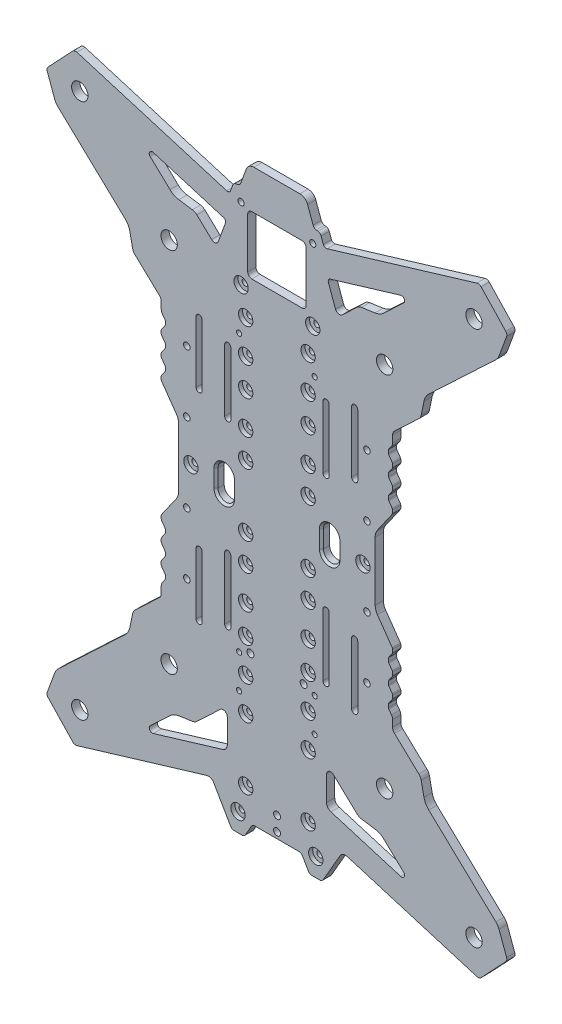
SolidWorks part; units mm, degrees
ref_plane "Front Plane" through (0, 0, 0) normal (0, 0, 1) x (1, 0, 0)
ref_plane "Top Plane" through (0, 0, 0) normal (0, 1, 0) x (1, 0, 0)
ref_plane "Right Plane" through (0, 0, 0) normal (1, 0, 0) x (0, 0, -1)
sketch "Model" plane through (0, 0, 0) normal (0, 0, 1) x (1, 0, 0)
  line L0 (183.8108, 197.417) -> (183.8108, 227.917)
  line L1 (186.8108, 227.917) -> (186.8108, 197.417)
  line L2 (138.8108, 139.917) -> (138.8108, 109.417)
  line L3 (135.8108, 109.417) -> (135.8108, 139.917)
  line L4 (186.8108, 139.917) -> (186.8108, 109.417)
  line L5 (183.8108, 109.417) -> (183.8108, 139.917)
  line L6 (135.8108, 197.417) -> (135.8108, 227.917)
  line L7 (138.8108, 227.917) -> (138.8108, 197.417)
  line L8 (147.0608, 264.0945) -> (147.0608, 288.5945)
  line L9 (173.5608, 262.0945) -> (149.0608, 262.0945)
  line L10 (175.5608, 288.5945) -> (175.5608, 264.0945)
  line L11 (149.0608, 290.5945) -> (173.5608, 290.5945)
  line L12 (133.6884, 72.3677) -> (122.1935, 61.5247)
  line L13 (120.0282, 60.4766) -> (113.4215, 59.5095)
  line L14 (100.8847, 45.7661) -> (134.926, 56.02)
  line L15 (209.2, 59.5095) -> (202.5933, 60.4766)
  line L16 (200.428, 61.5247) -> (188.9331, 72.3677)
  line L17 (185.5608, 58.8925) -> (185.5608, 70.9128)
  line L18 (187.6955, 56.02) -> (221.7368, 45.7661)
  line L19 (223.1987, 48.2935) -> (213.5306, 57.4133)
  line L20 (113.4215, 277.8244) -> (120.0282, 276.8573)
  line L21 (122.1935, 275.8092) -> (129.4288, 268.9842)
  line L22 (135.174, 281.2392) -> (100.8847, 291.5678)
  line L23 (99.4228, 289.0404) -> (109.0909, 279.9206)
  line L24 (261.0344, 314.783) -> (273.0616, 302.0327)
  line L25 (273.4849, 299.9728) -> (269.7846, 289.8648)
  line L26 (268.2674, 287.5628) -> (235.4884, 256.6428)
  line L27 (233.1432, 252.4417) -> (231.7925, 245.9027)
  line L28 (230.6199, 243.8022) -> (218.7522, 232.6075)
  line L29 (217.8108, 230.4252) -> (217.8108, 227.2161)
  line L30 (217.2682, 225.4954) -> (215.9916, 223.6722)
  line L31 (215.8108, 223.0986) -> (215.8108, 221.7292)
  line L32 (215.9916, 221.1557) -> (217.6299, 218.8159)
  line L33 (217.8108, 218.2423) -> (217.8108, 216.8729)
  line L34 (217.6299, 216.2994) -> (215.9916, 213.9596)
  line L35 (215.8108, 213.386) -> (215.8108, 212.0166)
  line L36 (215.9916, 211.4431) -> (217.6299, 209.1033)
  line L37 (217.8108, 208.5298) -> (217.8108, 207.1603)
  line L38 (217.6299, 206.5868) -> (215.9916, 204.247)
  line L39 (215.8108, 203.6735) -> (215.8108, 202.304)
  line L40 (215.9916, 201.7305) -> (217.6299, 199.3907)
  line L41 (217.8108, 198.8172) -> (217.8108, 197.4478)
  line L42 (217.6299, 196.8742) -> (210.3959, 186.5429)
  line L43 (209.3108, 183.1014) -> (209.3108, 154.2325)
  line L44 (210.3959, 150.791) -> (217.6299, 140.4597)
  line L45 (217.8108, 139.8861) -> (217.8108, 138.5167)
  line L46 (217.6299, 137.9432) -> (215.9916, 135.6034)
  line L47 (215.8108, 135.0299) -> (215.8108, 133.6605)
  line L48 (215.9916, 133.0869) -> (217.6299, 130.7471)
  line L49 (217.8108, 130.1736) -> (217.8108, 128.8042)
  line L50 (217.6299, 128.2306) -> (215.9916, 125.8908)
  line L51 (215.8108, 125.3173) -> (215.8108, 123.9479)
  line L52 (215.9916, 123.3743) -> (217.6299, 121.0345)
  line L53 (217.8108, 120.461) -> (217.8108, 119.0916)
  line L54 (217.6299, 118.518) -> (215.9916, 116.1782)
  line L55 (215.8108, 115.6047) -> (215.8108, 114.2353)
  line L56 (215.9916, 113.6617) -> (217.2682, 111.8385)
  line L57 (217.8108, 110.1178) -> (217.8108, 106.9087)
  line L58 (218.7522, 104.7264) -> (230.6199, 93.5317)
  line L59 (231.7925, 91.4312) -> (233.1432, 84.8922)
  line L60 (235.4884, 80.6911) -> (268.2674, 49.7711)
  line L61 (269.7846, 47.4691) -> (273.4849, 37.3611)
  line L62 (273.0616, 35.3012) -> (261.0344, 22.5509)
  line L63 (259.0027, 22.0083) -> (195.64, 41.0944)
  line L64 (192.1766, 39.7219) -> (183.942, 25.4591)
  line L65 (182.2099, 24.4591) -> (178.4116, 24.4591)
  line L66 (176.6796, 25.4591) -> (173.7928, 30.4591)
  line L67 (172.0608, 31.4591) -> (150.5608, 31.4591)
  line L68 (148.8287, 30.4591) -> (145.942, 25.4591)
  line L69 (144.2099, 24.4591) -> (140.4116, 24.4591)
  line L70 (138.6796, 25.4591) -> (130.4449, 39.7219)
  line L71 (126.9816, 41.0944) -> (63.6188, 22.0083)
  line L72 (61.5871, 22.5509) -> (49.5599, 35.3012)
  line L73 (49.1366, 37.3611) -> (52.8369, 47.4691)
  line L74 (54.3542, 49.7711) -> (87.1331, 80.6911)
  line L75 (89.4783, 84.8922) -> (90.8291, 91.4312)
  line L76 (92.0016, 93.5317) -> (103.8693, 104.7264)
  line L77 (104.8108, 106.9087) -> (104.8108, 110.1178)
  line L78 (105.3533, 111.8385) -> (106.6299, 113.6617)
  line L79 (106.8108, 114.2353) -> (106.8108, 115.6047)
  line L80 (106.6299, 116.1782) -> (104.9916, 118.518)
  line L81 (104.8108, 119.0916) -> (104.8108, 120.461)
  line L82 (104.9916, 121.0345) -> (106.6299, 123.3743)
  line L83 (106.6299, 125.8908) -> (104.9916, 128.2306)
  line L84 (104.8108, 128.8042) -> (104.8108, 130.1736)
  line L85 (104.9916, 130.7471) -> (106.6299, 133.0869)
  line L86 (106.8108, 133.6605) -> (106.8108, 135.0299)
  line L87 (106.6299, 135.6034) -> (104.9916, 137.9432)
  line L88 (104.8108, 138.5167) -> (104.8108, 139.8861)
  line L89 (104.9916, 140.4597) -> (112.2257, 150.791)
  line L90 (113.3108, 154.2325) -> (113.3108, 183.1014)
  line L91 (112.2257, 186.5429) -> (104.9916, 196.8742)
  line L92 (104.8108, 197.4478) -> (104.8108, 198.8172)
  line L93 (104.9916, 199.3907) -> (106.6299, 201.7305)
  line L94 (106.8108, 202.304) -> (106.8108, 203.6735)
  line L95 (106.6299, 204.247) -> (104.9916, 206.5868)
  line L96 (104.8108, 207.1603) -> (104.8108, 208.5298)
  line L97 (104.9916, 209.1033) -> (106.6299, 211.4431)
  line L98 (106.8108, 212.0166) -> (106.8108, 213.386)
  line L99 (106.6299, 213.9596) -> (104.9916, 216.2994)
  line L100 (104.8108, 216.8729) -> (104.8108, 218.2423)
  line L101 (104.9916, 218.8159) -> (106.6299, 221.1557)
  line L102 (106.8108, 221.7292) -> (106.8108, 223.0986)
  line L103 (106.6299, 223.6722) -> (105.3533, 225.4954)
  line L104 (104.8108, 227.2161) -> (104.8108, 230.4252)
  line L105 (103.8693, 232.6075) -> (92.0016, 243.8022)
  line L106 (90.8291, 245.9027) -> (89.4783, 252.4417)
  line L107 (87.1331, 256.6428) -> (54.3542, 287.5628)
  line L108 (52.8369, 289.8648) -> (49.1366, 299.9728)
  line L109 (49.5599, 302.0327) -> (61.5871, 314.783)
  line L110 (63.6188, 315.3256) -> (136.8099, 293.279)
  line L111 (138.6521, 294.2022) -> (139.728, 297.1583)
  line L112 (141.2601, 298.4439) -> (142.113, 298.5943)
  line L113 (143.6451, 299.8798) -> (146.325, 307.2429)
  line L114 (150.0838, 309.8748) -> (172.5378, 309.8748)
  line L115 (176.2965, 307.2429) -> (178.9765, 299.8798)
  line L116 (180.5086, 298.5943) -> (181.3614, 298.4439)
  line L117 (185.8116, 293.279) -> (259.0027, 315.3256)
  line L118 (193.1927, 268.9842) -> (200.428, 275.8092)
  line L119 (202.5933, 276.8573) -> (209.2, 277.8244)
  line L120 (221.7368, 291.5678) -> (187.4475, 281.2392)
  line L121 (186.4706, 279.2899) -> (189.941, 269.7551)
  line L122 (106.8108, 123.9479) -> (106.8108, 125.3173)
  line L123 (137.0608, 70.9128) -> (137.0608, 58.8925)
  line L124 (109.0909, 57.4133) -> (99.4228, 48.2935)
  line L125 (132.6805, 269.7551) -> (136.1509, 279.2899)
  line L126 (182.8935, 297.1583) -> (183.9694, 294.2022)
  line L127 (213.5306, 279.9206) -> (223.1987, 289.0404)
  circle A0 centre (178.8108, 292.022) radius 1.5
  arc A1 (183.8108, 197.417) -> (186.8108, 197.417) centre (185.3108, 197.417) ccw
  arc A2 (186.8108, 227.917) -> (183.8108, 227.917) centre (185.3108, 227.917) ccw
  arc A3 (138.8108, 139.917) -> (135.8108, 139.917) centre (137.3108, 139.917) ccw
  arc A4 (135.8108, 109.417) -> (138.8108, 109.417) centre (137.3108, 109.417) ccw
  circle A5 centre (213.9455, 258.3167) radius 4
  circle A6 centre (257.5914, 299.4875) radius 4
  circle A7 centre (65.0301, 299.4875) radius 4
  circle A8 centre (108.6761, 258.3167) radius 4
  circle A9 centre (108.6761, 79.0172) radius 4
  circle A10 centre (65.0301, 37.8464) radius 4
  circle A11 centre (257.5914, 37.8464) radius 4
  circle A12 centre (213.9455, 79.0172) radius 4
  arc A13 (186.8108, 139.917) -> (183.8108, 139.917) centre (185.3108, 139.917) ccw
  arc A14 (183.8108, 109.417) -> (186.8108, 109.417) centre (185.3108, 109.417) ccw
  arc A15 (135.8108, 197.417) -> (138.8108, 197.417) centre (137.3108, 197.417) ccw
  arc A16 (138.8108, 227.917) -> (135.8108, 227.917) centre (137.3108, 227.917) ccw
  circle A17 centre (143.8108, 292.022) radius 1.5
  arc A18 (147.0608, 264.0945) -> (149.0608, 262.0945) centre (149.0608, 264.0945) ccw
  arc A19 (173.5608, 262.0945) -> (175.5608, 264.0945) centre (173.5608, 264.0945) ccw
  arc A20 (175.5608, 288.5945) -> (173.5608, 290.5945) centre (173.5608, 288.5945) ccw
  arc A21 (149.0608, 290.5945) -> (147.0608, 288.5945) centre (149.0608, 288.5945) ccw
  circle A22 centre (146.0608, 227.917) radius 3.5 construction
  circle A23 centre (176.5608, 227.917) radius 3.5 construction
  circle A24 centre (176.5608, 197.417) radius 3.5 construction
  circle A25 centre (146.0608, 197.417) radius 3.5 construction
  circle A26 centre (119.3108, 168.667) radius 3.5 construction
  circle A27 centre (203.3108, 168.667) radius 3.5 construction
  circle A28 centre (146.0608, 183.917) radius 3.5 construction
  circle A29 centre (176.5608, 183.917) radius 3.5 construction
  circle A30 centre (146.0608, 153.417) radius 3.5 construction
  circle A31 centre (176.5608, 153.417) radius 3.5 construction
  circle A32 centre (146.0608, 139.917) radius 3.5 construction
  circle A33 centre (176.5608, 139.917) radius 3.5 construction
  circle A34 centre (146.0608, 109.417) radius 3.5 construction
  circle A35 centre (176.5608, 109.417) radius 3.5 construction
  circle A36 centre (146.0608, 76.667) radius 3.5 construction
  circle A37 centre (176.5608, 76.667) radius 3.5 construction
  circle A38 centre (146.0608, 46.167) radius 3.5 construction
  circle A39 centre (176.5608, 46.167) radius 3.5 construction
  circle A40 centre (142.3108, 33.4591) radius 3.5 construction
  circle A41 centre (180.3108, 33.4591) radius 3.5 construction
  circle A42 centre (176.5608, 93.042) radius 3.5 construction
  circle A43 centre (146.0608, 93.042) radius 3.5 construction
  circle A44 centre (176.5608, 123.542) radius 3.5 construction
  circle A45 centre (146.0608, 123.542) radius 3.5 construction
  circle A46 centre (176.5608, 213.792) radius 3.5 construction
  circle A47 centre (146.0608, 213.792) radius 3.5 construction
  circle A48 centre (176.5608, 244.292) radius 3.5 construction
  circle A49 centre (146.0608, 244.292) radius 3.5 construction
  circle A50 centre (178.8108, 257.022) radius 3.5 construction
  circle A51 centre (143.8108, 257.022) radius 3.5 construction
  arc A52 (137.0608, 70.9128) -> (133.6884, 72.3677) centre (135.0608, 70.9128) ccw
  arc A53 (120.0282, 60.4766) -> (122.1935, 61.5247) centre (119.4488, 64.4344) ccw
  arc A54 (113.4215, 59.5095) -> (109.0909, 57.4133) centre (114.5803, 51.5938) ccw
  arc A55 (99.4228, 48.2935) -> (100.8847, 45.7661) centre (100.4521, 47.2023) ccw
  arc A56 (134.926, 56.02) -> (137.0608, 58.8925) centre (134.0608, 58.8925) ccw
  arc A57 (200.428, 61.5247) -> (202.5933, 60.4766) centre (203.1727, 64.4344) ccw
  arc A58 (188.9331, 72.3677) -> (185.5608, 70.9128) centre (187.5608, 70.9128) ccw
  arc A59 (185.5608, 58.8925) -> (187.6955, 56.02) centre (188.5608, 58.8925) ccw
  arc A60 (221.7368, 45.7661) -> (223.1987, 48.2935) centre (222.1695, 47.2023) ccw
  arc A61 (213.5306, 57.4133) -> (209.2, 59.5095) centre (208.0412, 51.5938) ccw
  arc A62 (122.1935, 275.8092) -> (120.0282, 276.8573) centre (119.4488, 272.8995) ccw
  arc A63 (129.4288, 268.9842) -> (132.6805, 269.7551) centre (130.8012, 270.4391) ccw
  arc A64 (136.1509, 279.2899) -> (135.174, 281.2392) centre (134.7414, 279.8029) ccw
  arc A65 (100.8847, 291.5678) -> (99.4228, 289.0404) centre (100.4521, 290.1316) ccw
  arc A66 (109.0909, 279.9206) -> (113.4215, 277.8244) centre (114.5803, 285.7401) ccw
  arc A67 (261.0344, 314.783) -> (259.0027, 315.3256) centre (259.5795, 313.4106) ccw
  arc A68 (273.4849, 299.9728) -> (273.0616, 302.0327) centre (271.6068, 300.6603) ccw
  arc A69 (268.2674, 287.5628) -> (269.7846, 289.8648) centre (264.1503, 291.9274) ccw
  arc A70 (235.4884, 256.6428) -> (233.1432, 252.4417) centre (240.9778, 250.8233) ccw
  arc A71 (230.6199, 243.8022) -> (231.7925, 245.9027) centre (227.8752, 246.7119) ccw
  arc A72 (218.7522, 232.6075) -> (217.8108, 230.4252) centre (220.8108, 230.4252) ccw
  arc A73 (217.2682, 225.4954) -> (217.8108, 227.2161) centre (214.8108, 227.2161) ccw
  arc A74 (215.9916, 223.6722) -> (215.8108, 223.0986) centre (216.8108, 223.0986) ccw
  arc A75 (215.8108, 221.7292) -> (215.9916, 221.1557) centre (216.8108, 221.7292) ccw
  arc A76 (217.8108, 218.2423) -> (217.6299, 218.8159) centre (216.8108, 218.2423) ccw
  arc A77 (217.6299, 216.2994) -> (217.8108, 216.8729) centre (216.8108, 216.8729) ccw
  arc A78 (215.9916, 213.9596) -> (215.8108, 213.386) centre (216.8108, 213.386) ccw
  arc A79 (215.8108, 212.0166) -> (215.9916, 211.4431) centre (216.8108, 212.0166) ccw
  arc A80 (217.8108, 208.5298) -> (217.6299, 209.1033) centre (216.8108, 208.5298) ccw
  arc A81 (217.6299, 206.5868) -> (217.8108, 207.1603) centre (216.8108, 207.1603) ccw
  arc A82 (215.9916, 204.247) -> (215.8108, 203.6735) centre (216.8108, 203.6735) ccw
  arc A83 (215.8108, 202.304) -> (215.9916, 201.7305) centre (216.8108, 202.3041) ccw
  arc A84 (217.8108, 198.8172) -> (217.6299, 199.3907) centre (216.8108, 198.8172) ccw
  arc A85 (217.6299, 196.8742) -> (217.8108, 197.4478) centre (216.8108, 197.4478) ccw
  arc A86 (210.3959, 186.5429) -> (209.3108, 183.1014) centre (215.3108, 183.1014) ccw
  arc A87 (209.3108, 154.2325) -> (210.3959, 150.791) centre (215.3108, 154.2325) ccw
  arc A88 (217.8108, 139.8861) -> (217.6299, 140.4597) centre (216.8108, 139.8861) ccw
  arc A89 (217.6299, 137.9432) -> (217.8108, 138.5167) centre (216.8108, 138.5167) ccw
  arc A90 (215.9916, 135.6034) -> (215.8108, 135.0299) centre (216.8108, 135.0299) ccw
  arc A91 (215.8108, 133.6605) -> (215.9916, 133.0869) centre (216.8108, 133.6604) ccw
  arc A92 (217.8108, 130.1736) -> (217.6299, 130.7471) centre (216.8108, 130.1736) ccw
  arc A93 (217.6299, 128.2306) -> (217.8108, 128.8042) centre (216.8108, 128.8042) ccw
  arc A94 (215.9916, 125.8908) -> (215.8108, 125.3173) centre (216.8108, 125.3173) ccw
  arc A95 (215.8108, 123.9479) -> (215.9916, 123.3743) centre (216.8108, 123.9479) ccw
  arc A96 (217.8108, 120.461) -> (217.6299, 121.0345) centre (216.8108, 120.461) ccw
  arc A97 (217.6299, 118.518) -> (217.8108, 119.0916) centre (216.8108, 119.0916) ccw
  arc A98 (215.9916, 116.1782) -> (215.8108, 115.6047) centre (216.8108, 115.6047) ccw
  arc A99 (215.8108, 114.2353) -> (215.9916, 113.6617) centre (216.8108, 114.2353) ccw
  arc A100 (217.8108, 110.1178) -> (217.2682, 111.8385) centre (214.8108, 110.1178) ccw
  arc A101 (217.8108, 106.9087) -> (218.7522, 104.7264) centre (220.8108, 106.9087) ccw
  arc A102 (231.7925, 91.4312) -> (230.6199, 93.5317) centre (227.8752, 90.622) ccw
  arc A103 (233.1432, 84.8922) -> (235.4884, 80.6911) centre (240.9778, 86.5106) ccw
  arc A104 (269.7846, 47.4691) -> (268.2674, 49.7711) centre (264.1503, 45.4065) ccw
  arc A105 (273.0616, 35.3012) -> (273.4849, 37.3611) centre (271.6068, 36.6736) ccw
  arc A106 (259.0027, 22.0083) -> (261.0344, 22.5509) centre (259.5795, 23.9233) ccw
  arc A107 (195.64, 41.0944) -> (192.1766, 39.7219) centre (194.7747, 38.2219) ccw
  arc A108 (182.2099, 24.4591) -> (183.942, 25.4591) centre (182.2099, 26.4591) ccw
  arc A109 (176.6796, 25.4591) -> (178.4116, 24.4591) centre (178.4116, 26.4591) ccw
  arc A110 (173.7928, 30.4591) -> (172.0608, 31.4591) centre (172.0608, 29.4591) ccw
  arc A111 (150.5608, 31.4591) -> (148.8287, 30.4591) centre (150.5608, 29.4591) ccw
  arc A112 (144.2099, 24.4591) -> (145.942, 25.4591) centre (144.2099, 26.4591) ccw
  arc A113 (138.6796, 25.4591) -> (140.4116, 24.4591) centre (140.4116, 26.4591) ccw
  arc A114 (130.4449, 39.7219) -> (126.9816, 41.0944) centre (127.8468, 38.2219) ccw
  arc A115 (61.5871, 22.5509) -> (63.6188, 22.0083) centre (63.042, 23.9233) ccw
  arc A116 (49.1366, 37.3611) -> (49.5599, 35.3012) centre (51.0147, 36.6736) ccw
  arc A117 (54.3542, 49.7711) -> (52.8369, 47.4691) centre (58.4712, 45.4065) ccw
  arc A118 (87.1331, 80.6911) -> (89.4783, 84.8922) centre (81.6437, 86.5106) ccw
  arc A119 (92.0016, 93.5317) -> (90.8291, 91.4312) centre (94.7464, 90.622) ccw
  arc A120 (103.8693, 104.7264) -> (104.8108, 106.9087) centre (101.8108, 106.9087) ccw
  arc A121 (105.3533, 111.8385) -> (104.8108, 110.1178) centre (107.8108, 110.1178) ccw
  arc A122 (106.6299, 113.6617) -> (106.8108, 114.2353) centre (105.8108, 114.2353) ccw
  arc A123 (106.8108, 115.6047) -> (106.6299, 116.1782) centre (105.8108, 115.6047) ccw
  arc A124 (104.8108, 119.0916) -> (104.9916, 118.518) centre (105.8108, 119.0916) ccw
  arc A125 (104.9916, 121.0345) -> (104.8108, 120.461) centre (105.8108, 120.461) ccw
  arc A126 (106.6299, 123.3743) -> (106.8108, 123.9479) centre (105.8108, 123.9479) ccw
  arc A127 (106.8108, 125.3173) -> (106.6299, 125.8908) centre (105.8108, 125.3173) ccw
  arc A128 (104.8108, 128.8042) -> (104.9916, 128.2306) centre (105.8108, 128.8042) ccw
  arc A129 (104.9916, 130.7471) -> (104.8108, 130.1736) centre (105.8108, 130.1736) ccw
  arc A130 (106.6299, 133.0869) -> (106.8108, 133.6605) centre (105.8108, 133.6604) ccw
  arc A131 (106.8108, 135.0299) -> (106.6299, 135.6034) centre (105.8108, 135.0299) ccw
  arc A132 (104.8108, 138.5167) -> (104.9916, 137.9432) centre (105.8108, 138.5167) ccw
  arc A133 (104.9916, 140.4597) -> (104.8108, 139.8861) centre (105.8108, 139.8861) ccw
  arc A134 (112.2257, 150.791) -> (113.3108, 154.2325) centre (107.3108, 154.2325) ccw
  arc A135 (113.3108, 183.1014) -> (112.2257, 186.5429) centre (107.3108, 183.1014) ccw
  arc A136 (104.8108, 197.4478) -> (104.9916, 196.8742) centre (105.8108, 197.4478) ccw
  arc A137 (104.9916, 199.3907) -> (104.8108, 198.8172) centre (105.8108, 198.8172) ccw
  arc A138 (106.6299, 201.7305) -> (106.8108, 202.304) centre (105.8108, 202.3041) ccw
  arc A139 (106.8108, 203.6735) -> (106.6299, 204.247) centre (105.8108, 203.6735) ccw
  arc A140 (104.8108, 207.1603) -> (104.9916, 206.5868) centre (105.8108, 207.1603) ccw
  arc A141 (104.9916, 209.1033) -> (104.8108, 208.5298) centre (105.8108, 208.5298) ccw
  arc A142 (106.6299, 211.4431) -> (106.8108, 212.0166) centre (105.8108, 212.0166) ccw
  arc A143 (106.8108, 213.386) -> (106.6299, 213.9596) centre (105.8108, 213.386) ccw
  arc A144 (104.8108, 216.8729) -> (104.9916, 216.2994) centre (105.8108, 216.8729) ccw
  arc A145 (104.9916, 218.8159) -> (104.8108, 218.2423) centre (105.8108, 218.2423) ccw
  arc A146 (106.6299, 221.1557) -> (106.8108, 221.7292) centre (105.8108, 221.7292) ccw
  arc A147 (106.8108, 223.0986) -> (106.6299, 223.6722) centre (105.8108, 223.0986) ccw
  arc A148 (104.8108, 227.2161) -> (105.3533, 225.4954) centre (107.8108, 227.2161) ccw
  arc A149 (104.8108, 230.4252) -> (103.8693, 232.6075) centre (101.8108, 230.4252) ccw
  arc A150 (90.8291, 245.9027) -> (92.0016, 243.8022) centre (94.7464, 246.7119) ccw
  arc A151 (89.4783, 252.4417) -> (87.1331, 256.6428) centre (81.6437, 250.8233) ccw
  arc A152 (52.8369, 289.8648) -> (54.3542, 287.5628) centre (58.4712, 291.9274) ccw
  arc A153 (49.5599, 302.0327) -> (49.1366, 299.9728) centre (51.0147, 300.6603) ccw
  arc A154 (63.6188, 315.3256) -> (61.5871, 314.783) centre (63.042, 313.4106) ccw
  arc A155 (136.8099, 293.279) -> (138.6521, 294.2022) centre (137.2425, 294.7152) ccw
  arc A156 (141.2601, 298.4439) -> (139.728, 297.1583) centre (141.6074, 296.4743) ccw
  arc A157 (142.113, 298.5943) -> (143.6451, 299.8798) centre (141.7657, 300.5639) ccw
  arc A158 (150.0838, 309.8748) -> (146.325, 307.2429) centre (150.0838, 305.8748) ccw
  arc A159 (176.2965, 307.2429) -> (172.5378, 309.8748) centre (172.5378, 305.8748) ccw
  arc A160 (178.9765, 299.8798) -> (180.5086, 298.5943) centre (180.8559, 300.5639) ccw
  arc A161 (182.8935, 297.1583) -> (181.3614, 298.4439) centre (181.0141, 296.4743) ccw
  arc A162 (183.9694, 294.2022) -> (185.8116, 293.279) centre (185.379, 294.7152) ccw
  arc A163 (202.5933, 276.8573) -> (200.428, 275.8092) centre (203.1727, 272.8995) ccw
  arc A164 (209.2, 277.8244) -> (213.5306, 279.9206) centre (208.0412, 285.7401) ccw
  arc A165 (223.1987, 289.0404) -> (221.7368, 291.5678) centre (222.1695, 290.1316) ccw
  arc A166 (187.4475, 281.2392) -> (186.4706, 279.2899) centre (187.8801, 279.8029) ccw
  arc A167 (189.941, 269.7551) -> (193.1927, 268.9842) centre (191.8204, 270.4391) ccw
  circle A168 centre (176.5608, 227.917) radius 1.5
  circle A169 centre (146.0608, 227.917) radius 1.5
  circle A170 centre (146.0608, 123.542) radius 1.5
  circle A171 centre (176.5608, 123.542) radius 1.5
  circle A172 centre (146.0608, 93.042) radius 1.5
  circle A173 centre (176.5608, 93.042) radius 1.5
  circle A174 centre (180.3108, 33.4591) radius 1.5
  circle A175 centre (142.3108, 33.4591) radius 1.5
  circle A176 centre (176.5608, 76.667) radius 1.5
  circle A177 centre (146.0608, 76.667) radius 1.5
  circle A178 centre (146.0608, 109.417) radius 1.5
  circle A179 centre (119.3108, 168.667) radius 1.5
  circle A180 centre (176.5608, 139.917) radius 1.5
  circle A181 centre (146.0608, 139.917) radius 1.5
  circle A182 centre (146.0608, 213.792) radius 1.5
  circle A183 centre (176.5608, 213.792) radius 1.5
  circle A184 centre (176.5608, 109.417) radius 1.5
  circle A185 centre (176.5608, 197.417) radius 1.5
  circle A186 centre (176.5608, 244.292) radius 1.5
  circle A187 centre (203.3108, 168.667) radius 1.5
  circle A188 centre (143.8108, 257.022) radius 1.5
  circle A189 centre (178.8108, 257.022) radius 1.5
  circle A190 centre (146.0608, 244.292) radius 1.5
  circle A191 centre (146.0608, 46.167) radius 1.5
  circle A192 centre (146.0608, 197.417) radius 1.5
  circle A193 centre (176.5608, 46.167) radius 1.5
  circle A194 centre (146.0608, 183.917) radius 1.5
  circle A195 centre (146.0608, 153.417) radius 1.5
  circle A196 centre (176.5608, 153.417) radius 1.5
  circle A197 centre (176.5608, 183.917) radius 1.5
extrude "Main Body" add sketch "Model" along normal blind 4
sketch "Sketch2" plane through (0, 0, 4) normal (0, 0, 1) x (1, 0, 0)
  circle A0 centre (176.5608, 46.167) radius 3.5 construction
  circle A1 centre (180.3108, 33.4591) radius 3.5 construction
  circle A2 centre (142.3108, 33.4591) radius 3.5 construction
  circle A3 centre (146.0608, 46.167) radius 3.5 construction
  circle A4 centre (176.5608, 76.667) radius 3.5 construction
  circle A5 centre (146.0608, 76.667) radius 3.5 construction
  circle A6 centre (146.0608, 93.042) radius 3.5 construction
  circle A7 centre (176.5608, 93.042) radius 3.5 construction
  circle A8 centre (176.5608, 109.417) radius 3.5 construction
  circle A9 centre (146.0608, 109.417) radius 3.5 construction
  circle A10 centre (176.5608, 123.542) radius 3.5 construction
  circle A11 centre (146.0608, 123.542) radius 3.5 construction
  circle A12 centre (146.0608, 139.917) radius 3.5 construction
  circle A13 centre (176.5608, 139.917) radius 3.5 construction
  circle A14 centre (176.5608, 139.917) radius 1.5 construction
  circle A15 centre (203.3108, 168.667) radius 3.5 construction
  circle A16 centre (176.5608, 153.417) radius 3.5 construction
  circle A17 centre (146.0608, 153.417) radius 3.5 construction
  circle A18 centre (119.3108, 168.667) radius 3.5 construction
  circle A19 centre (146.0608, 183.917) radius 3.5 construction
  circle A20 centre (176.5608, 183.917) radius 3.5 construction
  circle A21 centre (176.5608, 197.417) radius 3.5 construction
  circle A22 centre (146.0608, 197.417) radius 3.5 construction
  circle A23 centre (176.5608, 213.792) radius 3.5 construction
  circle A24 centre (146.0608, 213.792) radius 3.5 construction
  circle A25 centre (146.0608, 227.917) radius 3.5 construction
  circle A26 centre (176.5608, 227.917) radius 3.5 construction
  circle A27 centre (176.5608, 244.292) radius 3.5 construction
  circle A28 centre (178.8108, 257.022) radius 3.5 construction
  circle A29 centre (146.0608, 244.292) radius 3.5 construction
  circle A30 centre (143.8108, 257.022) radius 3.5 construction
  circle A31 centre (176.5608, 46.167) radius 3.5
  circle A32 centre (180.3108, 33.4591) radius 3.5
  circle A33 centre (142.3108, 33.4591) radius 3.5
  circle A34 centre (146.0608, 46.167) radius 3.5
  circle A35 centre (176.5608, 76.667) radius 3.5
  circle A36 centre (146.0608, 76.667) radius 3.5
  circle A37 centre (146.0608, 93.042) radius 3.5
  circle A38 centre (176.5608, 93.042) radius 3.5
  circle A39 centre (176.5608, 109.417) radius 3.5
  circle A40 centre (146.0608, 109.417) radius 3.5
  circle A41 centre (176.5608, 123.542) radius 3.5
  circle A42 centre (146.0608, 123.542) radius 3.5
  circle A43 centre (146.0608, 139.917) radius 3.5
  circle A44 centre (176.5608, 139.917) radius 3.5
  circle A45 centre (176.5608, 139.917) radius 1.5
  circle A46 centre (203.3108, 168.667) radius 3.5
  circle A47 centre (176.5608, 153.417) radius 3.5
  circle A48 centre (146.0608, 153.417) radius 3.5
  circle A49 centre (119.3108, 168.667) radius 3.5
  circle A50 centre (146.0608, 183.917) radius 3.5
  circle A51 centre (176.5608, 183.917) radius 3.5
  circle A52 centre (176.5608, 197.417) radius 3.5
  circle A53 centre (146.0608, 197.417) radius 3.5
  circle A54 centre (176.5608, 213.792) radius 3.5
  circle A55 centre (146.0608, 213.792) radius 3.5
  circle A56 centre (146.0608, 227.917) radius 3.5
  circle A57 centre (176.5608, 227.917) radius 3.5
  circle A58 centre (176.5608, 244.292) radius 3.5
  circle A59 centre (178.8108, 257.022) radius 3.5
  circle A60 centre (146.0608, 244.292) radius 3.5
  circle A61 centre (143.8108, 257.022) radius 3.5
extrude "  Lower Fixture Point Countersink" cut sketch "Sketch2" against normal blind 2
sketch "Sketch3" plane through (0, 0, 0) normal (0, 0, -1) x (-1, 0, 0)
  line L0 (-124.8108, 134.6669) -> (-124.8108, 104.6669) construction
  line L1 (-121.8108, 104.6669) -> (-121.8108, 134.6669) construction
  line L2 (-124.8108, 232.667) -> (-124.8108, 202.667) construction
  line L3 (-121.8108, 202.667) -> (-121.8108, 232.667) construction
  line L4 (-200.8108, 232.667) -> (-200.8108, 202.667) construction
  line L5 (-197.8108, 202.667) -> (-197.8108, 232.667) construction
  line L6 (-197.8108, 104.6669) -> (-197.8108, 134.6669) construction
  line L7 (-200.8108, 134.6669) -> (-200.8108, 104.6669) construction
  line L8 (-124.8108, 134.6669) -> (-124.8108, 104.6669)
  line L9 (-121.8108, 104.6669) -> (-121.8108, 134.6669)
  line L10 (-124.8108, 232.667) -> (-124.8108, 202.667)
  line L11 (-121.8108, 202.667) -> (-121.8108, 232.667)
  line L12 (-200.8108, 232.667) -> (-200.8108, 202.667)
  line L13 (-197.8108, 202.667) -> (-197.8108, 232.667)
  line L14 (-197.8108, 104.6669) -> (-197.8108, 134.6669)
  line L15 (-200.8108, 134.6669) -> (-200.8108, 104.6669)
  arc A0 (-124.8108, 104.6669) -> (-121.8108, 104.6669) centre (-123.3108, 104.6669) ccw construction
  arc A1 (-121.8108, 134.6669) -> (-124.8108, 134.6669) centre (-123.3108, 134.6669) ccw construction
  arc A2 (-124.8108, 202.667) -> (-121.8108, 202.667) centre (-123.3108, 202.667) ccw construction
  arc A3 (-121.8108, 232.667) -> (-124.8108, 232.667) centre (-123.3108, 232.667) ccw construction
  arc A4 (-197.8108, 232.667) -> (-200.8108, 232.667) centre (-199.3108, 232.667) ccw construction
  arc A5 (-200.8108, 202.667) -> (-197.8108, 202.667) centre (-199.3108, 202.667) ccw construction
  arc A6 (-200.8108, 104.6669) -> (-197.8108, 104.6669) centre (-199.3108, 104.6669) ccw construction
  arc A7 (-197.8108, 134.6669) -> (-200.8108, 134.6669) centre (-199.3108, 134.6669) ccw construction
  arc A8 (-124.8108, 104.6669) -> (-121.8108, 104.6669) centre (-123.3108, 104.6669) ccw
  arc A9 (-121.8108, 134.6669) -> (-124.8108, 134.6669) centre (-123.3108, 134.6669) ccw
  arc A10 (-124.8108, 202.667) -> (-121.8108, 202.667) centre (-123.3108, 202.667) ccw
  arc A11 (-121.8108, 232.667) -> (-124.8108, 232.667) centre (-123.3108, 232.667) ccw
  arc A12 (-197.8108, 232.667) -> (-200.8108, 232.667) centre (-199.3108, 232.667) ccw
  arc A13 (-200.8108, 202.667) -> (-197.8108, 202.667) centre (-199.3108, 202.667) ccw
  arc A14 (-200.8108, 104.6669) -> (-197.8108, 104.6669) centre (-199.3108, 104.6669) ccw
  arc A15 (-197.8108, 134.6669) -> (-200.8108, 134.6669) centre (-199.3108, 134.6669) ccw
extrude "Extra Battery Strap Fixtures" cut sketch "Sketch3" against normal up to next
sketch "Sketch4" plane through (0, 0, 0) normal (0, 0, -1) x (-1, 0, 0)
  line L0 (-187.0608, 164.417) -> (-187.0608, 172.917) construction
  line L1 (-191.0608, 164.417) -> (-191.0608, 172.917)
  line L2 (-183.0608, 164.417) -> (-183.0608, 172.917)
  line L3 (-135.5608, 172.917) -> (-135.5608, 164.417) construction
  line L4 (-131.5608, 172.917) -> (-131.5608, 164.417)
  line L5 (-139.5608, 172.917) -> (-139.5608, 164.417)
  circle A0 centre (-187.0608, 172.917) radius 1.6 construction
  circle A1 centre (-187.0608, 164.417) radius 1.6 construction
  circle A2 centre (-135.5608, 172.917) radius 1.6 construction
  circle A3 centre (-135.5608, 164.417) radius 1.6 construction
  circle A4 centre (-187.0608, 172.917) radius 1.6 construction
  circle A5 centre (-187.0608, 164.417) radius 1.6 construction
  circle A6 centre (-135.5608, 172.917) radius 1.6 construction
  circle A7 centre (-135.5608, 164.417) radius 1.6 construction
  arc A8 (-191.0608, 164.417) -> (-183.0608, 164.417) centre (-187.0608, 164.417) ccw
  arc A9 (-183.0608, 172.917) -> (-191.0608, 172.917) centre (-187.0608, 172.917) ccw
  arc A10 (-131.5608, 172.917) -> (-139.5608, 172.917) centre (-135.5608, 172.917) ccw
  arc A11 (-139.5608, 164.417) -> (-131.5608, 164.417) centre (-135.5608, 164.417) ccw
  point P12 (-187.0608, 168.667)
  point P17 (-135.5608, 168.667)
  dimension "D1" = 8
extrude "Battery Cable Ingress" cut sketch "Sketch4" against normal up to next
chamfer "Battery Cable Ingress Chamfer" distance 1 angle 45 4 edges at (131.5608, 168.667, 4) (139.5608, 168.667, 4) (183.0608, 168.667, 4) (191.0608, 168.667, 4) tangent propagation no
sketch "Sketch5" plane through (0, 0, 0) normal (0, 0, -1) x (-1, 0, 0)
  line L0 (-161.3108, 262.0945) -> (-161.3108, 31.4591) construction
  line L1 (-149.0608, 262.0945) -> (-173.5608, 262.0945) construction
  line L2 (-150.5608, 31.4591) -> (-172.0608, 31.4591) construction
  line L3 (-146.0608, 109.417) -> (-146.0608, 93.042) construction
  line L4 (-146.0608, 93.042) -> (-146.0608, 76.667) construction
  line L5 (-179.7608, 101.2295) -> (-142.8608, 101.2295) construction
  line L6 (-179.7608, 84.8545) -> (-142.8608, 84.8545) construction
  line L7 (-179.7608, 236.1045) -> (-142.8608, 236.1045) construction
  line L8 (-146.0608, 244.292) -> (-146.0608, 227.917) construction
  circle A4 centre (-142.8608, 84.8545) radius 1.25
  circle A5 centre (-142.8608, 101.2295) radius 1.25
  circle A6 centre (-142.8608, 236.1045) radius 1.25
  circle A7 centre (-179.7608, 236.1045) radius 1.25
  circle A8 centre (-179.7608, 101.2295) radius 1.25
  circle A9 centre (-179.7608, 84.8545) radius 1.25
  point P24 (-146.0608, 84.8545)
  point P25 (-146.0608, 101.2295)
  point P30 (-146.0608, 236.1045)
  dimension "D1" = 2.5
  dimension "D2" = 36.9
  dimension "D3" = 36.9
  dimension "D4" = 36.9
extrude "Mauch PL200 Mounting Points" cut sketch "Sketch5" against normal up to next
sketch "Sketch6" plane through (0, 0, 0) normal (0, 0, -1) x (-1, 0, 0)
  circle A0 centre (-174.3688, 103.4113) radius 1.7 construction
  circle A1 centre (-148.3688, 103.4113) radius 1.7 construction
  circle A2 centre (-161.3688, 34.4113) radius 1.7 construction
  circle A3 centre (-161.3688, 41.4113) radius 2.25 construction
  circle A4 centre (-174.3688, 103.4113) radius 1.7
  circle A5 centre (-148.3688, 103.4113) radius 1.7
  circle A6 centre (-161.3688, 34.4113) radius 1.7
  circle A7 centre (-161.3688, 41.4113) radius 2.25 construction
  circle A8 centre (-161.3688, 41.4113) radius 1.7
  dimension "D1" = 3.4
extrude "RFD Carrier Mounting Points" cut sketch "Sketch6" against normal up to next
sketch "Sketch7" plane through (0, 0, 0) normal (0, 0, -1) x (-1, 0, 0)
  circle A0 centre (-205.3108, 217.8895) radius 1.6 construction
  circle A1 centre (-205.3108, 187.8895) radius 1.6 construction
  circle A2 centre (-205.3108, 149.3895) radius 1.6 construction
  circle A3 centre (-205.3108, 119.3895) radius 1.6 construction
  circle A4 centre (-117.3108, 119.3895) radius 1.6 construction
  circle A5 centre (-117.3108, 149.3895) radius 1.6 construction
  circle A6 centre (-117.3108, 187.8895) radius 1.6 construction
  circle A7 centre (-117.3108, 217.8895) radius 1.6 construction
  circle A8 centre (-205.3108, 217.8895) radius 1.6
  circle A9 centre (-205.3108, 187.8895) radius 1.6
  circle A10 centre (-205.3108, 149.3895) radius 1.6
  circle A11 centre (-205.3108, 119.3895) radius 1.6
  circle A12 centre (-117.3108, 119.3895) radius 1.6
  circle A13 centre (-117.3108, 149.3895) radius 1.6
  circle A14 centre (-117.3108, 187.8895) radius 1.6
  circle A15 centre (-117.3108, 217.8895) radius 1.6
extrude "ESC Carrier Fixtures Points" cut sketch "Sketch7" against normal up to next
